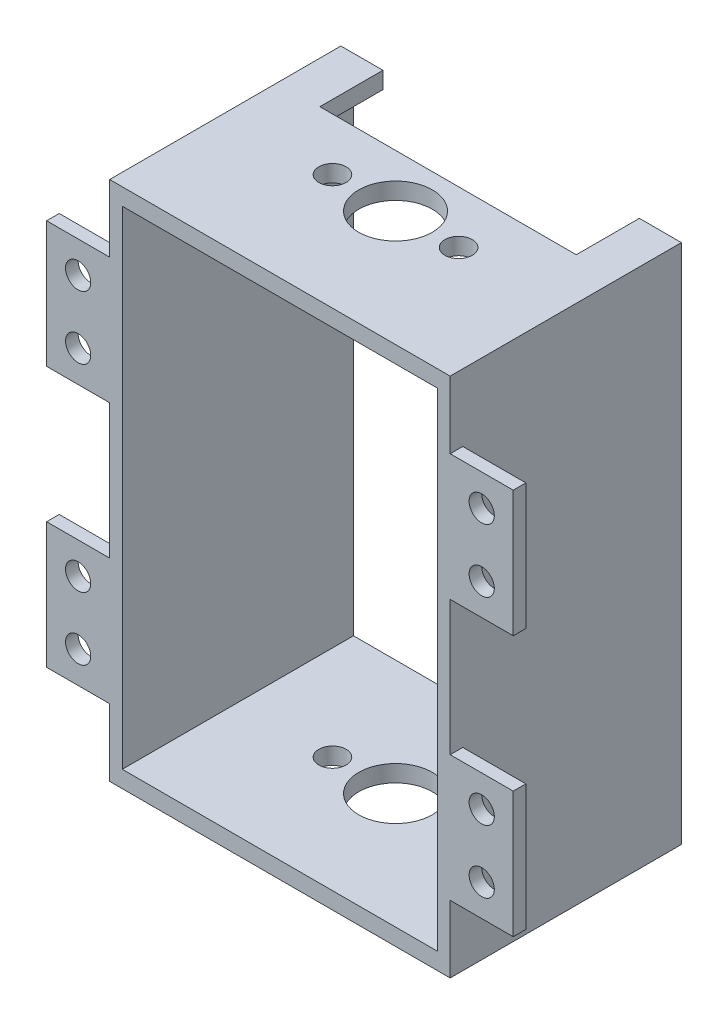
SolidWorks part; units mm, degrees
ref_plane "Front Plane" through (0, 0, 0) normal (0, 0, 1) x (1, 0, 0)
ref_plane "Top Plane" through (0, 0, 0) normal (0, 1, 0) x (1, 0, 0)
ref_plane "Right Plane" through (0, 0, 0) normal (1, 0, 0) x (0, 0, -1)
sketch "Sketch1" plane through (0, 0, 0) normal (0, 1, 0) x (1, 0, 0)
  line L0 (37.5, 55) -> (37.5, 0) construction
  line L1 (0, 0) -> (75, 0)
  line L2 (0, 0) -> (0, 55)
  line L3 (0, 55) -> (75, 55)
  line L4 (75, 0) -> (75, 55)
  line L5 (0, 27.5) -> (37.5, 27.5) construction
  line L6 (37.5, 27.5) -> (75, 27.5) construction
  circle A2 centre (37.5, 27.5) radius 8.75
  circle A5 centre (22.5, 27.5) radius 3.25
  circle A6 centre (52.5, 27.5) radius 3.25
  dimension "D2" = 6.5
  dimension "D3" = 17.5
  dimension "D1" = 55
  dimension "D4" = 75
  dimension "D5" = 15
extrude "Boss-Extrude1" add sketch "Sketch1" along normal blind 4
sketch "Sketch2" plane through (0, 0, 0) normal (-1, 0, 0) x (0, 0, 1)
  line L0 (-55, 4) -> (-55, 0) construction
  line L1 (0, 0) -> (-55, 0)
  line L2 (0, 0) -> (0, 120)
  line L3 (0, 120) -> (-55, 120)
  line L4 (-55, 0) -> (-55, 120)
  dimension "D1" = 120
extrude "Boss-Extrude2" add sketch "Sketch2" along normal blind 3
ref_plane "Plane1" through (37.5, 0, 0) normal (1, 0, 0) x (0, 0, -1)
mirror "Mirror1" about plane through (37.5, 0, 0) normal (1, 0, 0) of "Boss-Extrude2"
sketch "Sketch3" plane through (0, 120, 0) normal (0, 1, 0) x (1, 0, 0)
  line L1 (-3, 0) -> (78, 0)
  line L2 (-3, 0) -> (-3, 55)
  line L3 (-3, 55) -> (78, 55)
  line L4 (78, 0) -> (78, 55)
  circle A1 centre (37.5, 27.5) radius 8.75
  circle A2 centre (22.5, 27.5) radius 3.25
  circle A3 centre (22.5, 27.5) radius 3.25 construction
  circle A4 centre (52.5, 27.5) radius 3.25
  circle A5 centre (52.5, 27.5) radius 3.25 construction
  circle A6 centre (37.5, 27.5) radius 8.75 construction
extrude "Boss-Extrude3" add sketch "Sketch3" along normal blind 4
sketch "Sketch5" plane through (0, 0, 0) normal (0, 0, 1) x (1, 0, 0)
  line L0 (78, 62) -> (-3, 62) construction
  line L1 (78, 0) -> (78, 124) construction
  line L2 (-3, 0) -> (-3, 124) construction
  line L3 (78, 124) -> (-3, 62) construction
  line L4 (-3, 78) -> (-18, 78)
  line L5 (-3, 78) -> (-3, 108)
  line L6 (-3, 108) -> (-18, 108)
  line L7 (-18, 78) -> (-18, 108)
  line L8 (-3, 108) -> (-18, 93) construction
  line L9 (-18, 93) -> (-3, 93) construction
  line L10 (-3, 16) -> (-18, 16)
  line L11 (-18, 46) -> (-18, 16)
  line L12 (-3, 46) -> (-18, 46)
  line L13 (-3, 46) -> (-3, 16)
  circle A0 centre (-10.5, 100.5) radius 3
  circle A1 centre (-10.5, 85.5) radius 3
  circle A2 centre (-10.5, 38.5) radius 3
  circle A3 centre (-10.5, 23.5) radius 3
  point P11 (37.5, 93)
  point P13 (-3, 93)
  dimension "D3" = 6
  dimension "D1" = 15
  dimension "D2" = 30
extrude "Boss-Extrude5" add sketch "Sketch5" against normal blind 3
mirror "Mirror2" about plane through (37.5, 0, 0) normal (1, 0, 0) of "Boss-Extrude5"
sketch "Sketch6" plane through (0, 124, 0) normal (0, 1, 0) x (1, 0, 0)
  line L0 (37.5, 55) -> (37.5, 0) construction
  line L1 (78, 55) -> (-3, 55) construction
  line L2 (-3, 0) -> (78, 0) construction
  line L4 (7, 55) -> (68, 55)
  line L5 (7, 55) -> (7, 40)
  line L6 (7, 40) -> (68, 40)
  line L7 (68, 55) -> (68, 40)
  line L11 (-3, 55) -> (-3, 0) construction
  point P10 (37.5, 55)
  dimension "D1" = 10
  dimension "D2" = 15
extrude "Cut-Extrude1" cut sketch "Sketch6" against normal up to next
equation "\"length\"=120"
equation "\"D1@Sketch2\"=\"length\""
equation "\"D3@LPattern1\"=\"length\""
